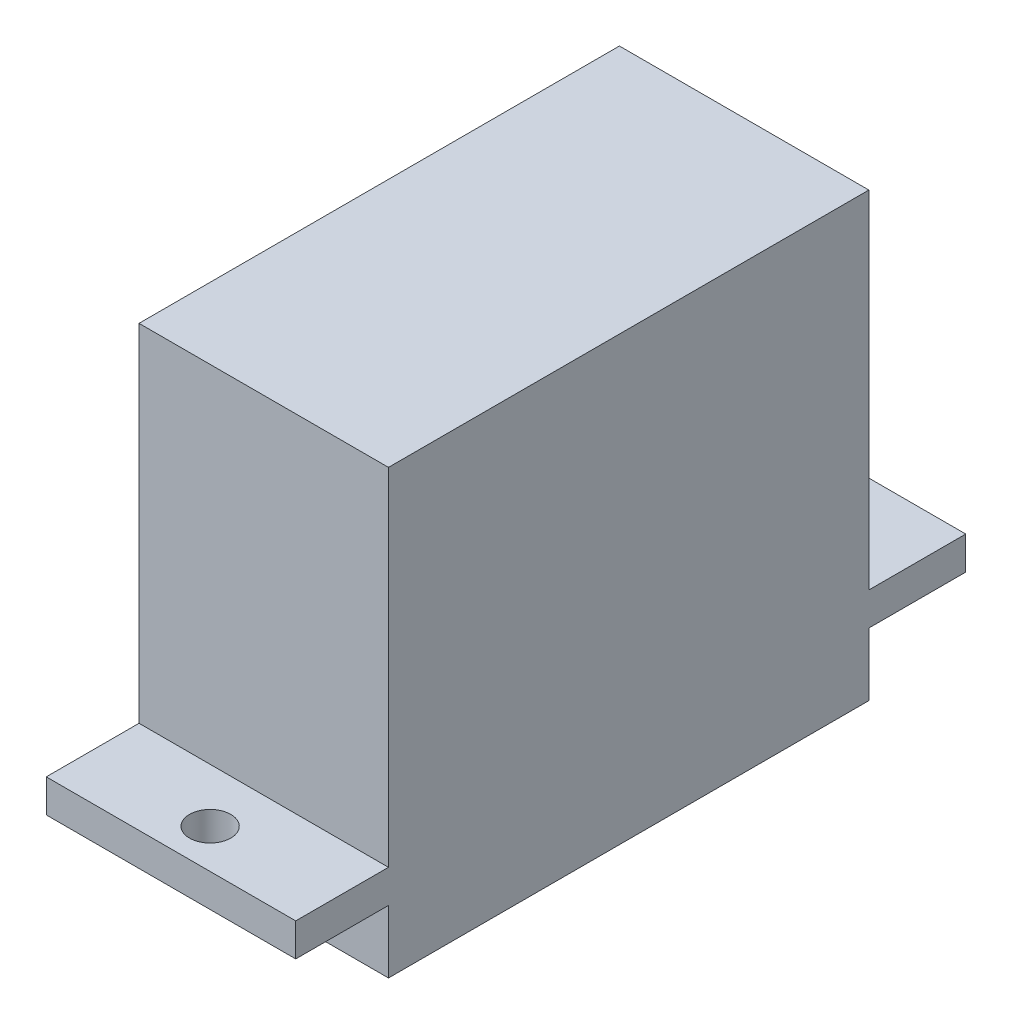
SolidWorks part; units mm, degrees
ref_plane "前视基准面" through (0, 0, 0) normal (0, 0, 1) x (1, 0, 0)
ref_plane "上视基准面" through (0, 0, 0) normal (0, 1, 0) x (1, 0, 0)
ref_plane "右视基准面" through (0, 0, 0) normal (1, 0, 0) x (0, 0, -1)
other "Configuration Table"
sketch "草图3" plane through (0, 0, 0) normal (1, 0, 0) x (0, 0, -1)
  line L1 (-16.8485, -8.5159) -> (15.6515, -8.5159)
  line L2 (-16.8485, -8.5159) -> (-16.8485, 12.9341)
  line L3 (-16.8485, 12.9341) -> (15.6515, 12.9341)
  line L4 (15.6515, -8.5159) -> (15.6515, 12.9341)
  dimension "D1" = 32.5
  dimension "D2" = 21.45
  dimension "D3" = 15.6515
  dimension "D4" = 12.9341
extrude "凸台-拉伸1" add sketch "草图3" along normal mid plane 12.1
sketch "草图4" plane through (0, 0, 0) normal (0, 1, 0) x (1, 0, 0)
  line L0 (0, 0) -> (15.913, 0) construction
  line L1 (-6.05, 10.9515) -> (6.05, 10.9515)
  line L2 (-6.05, 10.9515) -> (-6.05, 15.6516)
  line L3 (-6.05, 15.6516) -> (6.05, 15.6516)
  line L4 (6.05, 10.9515) -> (6.05, 15.6516)
  line L6 (-6.05, -16.9484) -> (6.05, -16.9484)
  line L7 (-6.05, -16.9484) -> (-6.05, -12.3484)
  line L8 (-6.05, -12.3484) -> (6.05, -12.3484)
  line L9 (6.05, -16.9484) -> (6.05, -12.3484)
  dimension "D1" = 12.1
  dimension "D2" = 4.7
  dimension "D3" = 10.9515
  dimension "D4" = 6.05
  dimension "D5" = 4.6
  dimension "D6" = 12.1
  dimension "D7" = 6.05
  dimension "D8" = 12.3484
extrude "切除-拉伸1" cut sketch "草图4" along normal through all from offset 3.8658 offset against normal yes
extrude "切除-拉伸2" cut sketch "草图4<2>" against normal through all from offset 5.4658 offset against normal yes
sketch "草图4<2>" plane through (0, 0, 0) normal (0, 1, 0) x (1, 0, 0) same geometry as "草图4"
sketch "草图5" plane through (0, 0, 0) normal (0, 1, 0) x (1, 0, 0)
  circle A0 centre (0, 13.55) radius 1
  circle A1 centre (0, -14.9492) radius 1
  dimension "D1" = 2
  dimension "D2" = 13.55
  dimension "D3" = 2
  dimension "D4" = 14.9492
extrude "切除-拉伸3" cut sketch "草图5" against normal through all
sketch "草图7" plane through (0, -8.5159, 0) normal (0, -1, 0) x (1, 0, 0)
  circle A0 centre (0, -7.6435) radius 1.049
  circle A1 centre (0, -7.6435) radius 1.5578
extrude "凸台-拉伸3" add sketch "草图7" along normal blind 3
